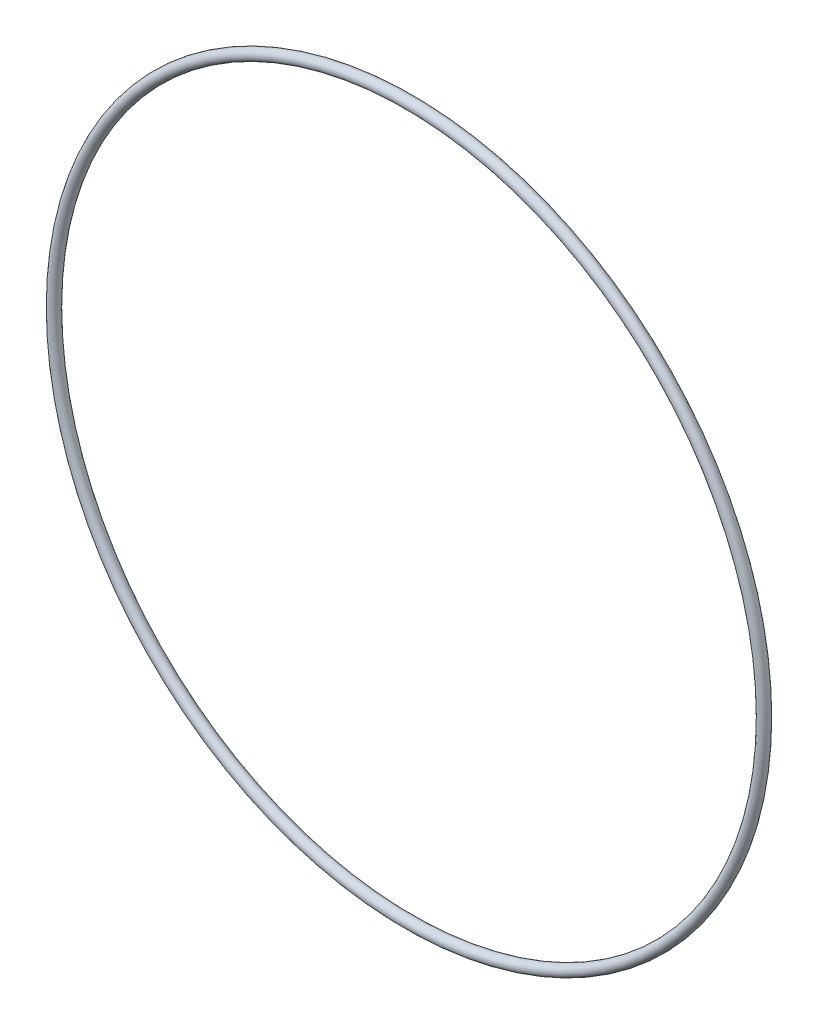
SolidWorks part; units mm, degrees
ref_plane "Front" through (0, 0, 0) normal (0, 0, 1) x (1, 0, 0)
ref_plane "Top" through (0, 0, 0) normal (0, 1, 0) x (1, 0, 0)
ref_plane "Right" through (0, 0, 0) normal (1, 0, 0) x (0, 0, -1)
sketch "Sketch1" plane through (0, 0, 0) normal (1, 0, 0) x (0, -1, 0)
  line L0 (0, -0.889) -> (0, 0.889) construction
  line L2 (-64.6671, 0) -> (64.6671, 0) construction
  line L3 (-57.0103, 0) -> (57.0103, 0) construction
  circle A0 centre (57.8993, 0) radius 0.889
  point P9 (57.0103, 0)
  point P10 (58.7883, 0)
  point P13 (57.8993, 0.889)
  point P14 (57.8993, -0.889)
  dimension "Width" = 1.778
  dimension "ID" = 114.0206
revolve "Revolve1" add sketch "Sketch1" angle 360 about L0
ref_axis "Axis1" through (0, 0, -0.9779) along (0, 0, 1)
